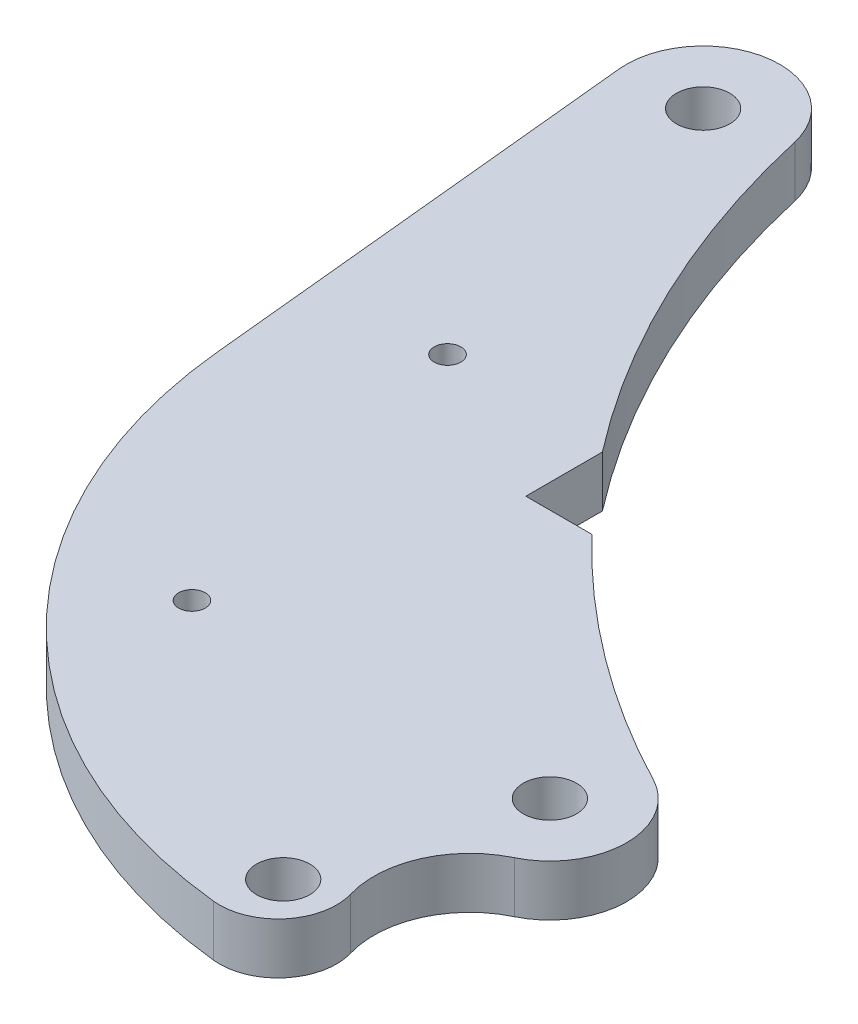
SolidWorks part; units mm, degrees
ref_plane "Front" through (0, 0, 0) normal (0, 0, 1) x (1, 0, 0)
ref_plane "Top" through (0, 0, 0) normal (0, 1, 0) x (1, 0, 0)
ref_plane "Right" through (0, 0, 0) normal (1, 0, 0) x (0, 0, -1)
ref_axis "side-side" through (80.9, 0, 0) along (-1, 0, 0)
ref_axis "up-down" through (0, 50, 0) along (0, -1, 0)
ref_axis "front-back" through (0, 0, -80.9) along (0, 0, 1)
sketch "Sketch1" plane through (0, 0, 0) normal (0, 1, 0) x (1, 0, 0)
  line L1 (54.5672, -104.6448) -> (42.2759, -98.926) construction
  line L2 (0, -50) -> (0, 50) construction
  line L3 (-9.0992, -0.9037) -> (-3.8076, -54.1854)
  line L4 (29.464, -41.4763) -> (29.464, -50.6079)
  line L5 (29.464, -50.6079) -> (37.3479, -50.6079)
  line L7 (35.56, -49.5919) -> (29.464, -49.5919) construction
  line L8 (29.464, -49.5919) -> (29.464, -62.2919) construction
  circle A0 centre (0, 0) radius 3.175
  circle A1 centre (62.123, -80.3946) radius 3.175
  circle A2 centre (54.5672, -104.6448) radius 3.175
  arc A3 (8.915, 2.0335) -> (29.464, -41.4763) centre (117.8765, 26.8869) ccw
  arc A4 (66.1053, -88.6259) -> (66.3397, -72.2809) centre (62.123, -80.3946) ccw
  arc A5 (52.6784, -111.055) -> (60.1172, -102.1389) centre (53.4158, -104.109) ccw
  arc A6 (60.1172, -102.1389) -> (66.1053, -88.6259) centre (71.0831, -98.915) cw
  arc A7 (8.915, 2.0335) -> (-9.0992, -0.9037) centre (0, 0) ccw
  arc A8 (52.6784, -111.055) -> (-3.8076, -54.1854) centre (59.3816, -47.9098) cw
  circle A9 centre (10.16, -40.64) radius 1.5875 construction
  circle A10 centre (20.32, -81.28) radius 1.5875 construction
  circle A11 centre (10.16, -40.64) radius 1.5875
  circle A12 centre (20.32, -81.28) radius 1.5875
  arc A13 (37.3479, -50.6079) -> (66.3397, -72.2809) centre (117.8765, 26.8869) ccw
  dimension "D1" = 6.35
  dimension "D2" = 2.54
  dimension "D3" = 18.288
  dimension "D4" = 13.97
  dimension "D6" = 11.43
  dimension "D7" = 111.76
  dimension "D9" = 63.5
  dimension "D5" = 65.049
  dimension "D8" = 5.672
  dimension "D10" = 1.016
extrude "Boss-Extrude1" add sketch "Sketch1" along normal mid plane 6.096
